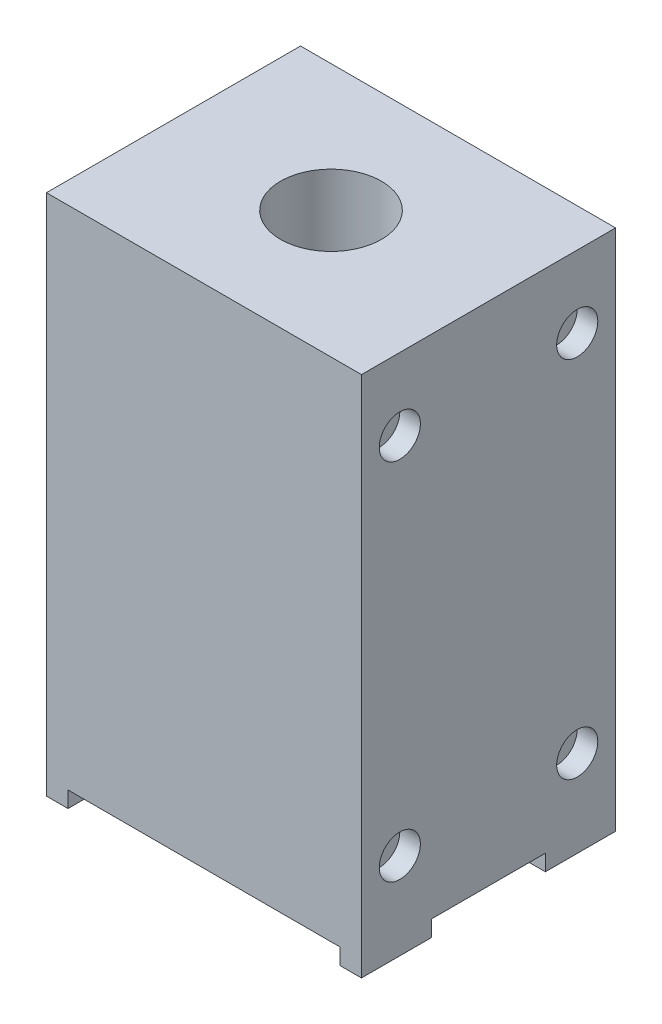
SolidWorks part; units mm, degrees
ref_plane "Front Plane" through (0, 0, 0) normal (0, 0, 1) x (1, 0, 0)
ref_plane "Top Plane" through (0, 0, 0) normal (0, 1, 0) x (1, 0, 0)
ref_plane "Right Plane" through (0, 0, 0) normal (1, 0, 0) x (0, 0, -1)
sketch "Sketch2" plane through (0, 0, 0) normal (0, 1, 0) x (1, 0, 0)
  line L1 (-15.325, 12.36) -> (15.325, 12.36)
  line L2 (-15.325, 12.36) -> (-15.325, -12.36)
  line L3 (-15.325, -12.36) -> (15.325, -12.36)
  line L4 (15.325, 12.36) -> (15.325, -12.36)
  line L5 (-15.325, 12.36) -> (15.325, -12.36) construction
  line L6 (-15.325, -12.36) -> (15.325, 12.36) construction
  point P0 (0, 0)
  dimension "D1" = 24.72
  dimension "D2" = 30.65
extrude "Boss-Extrude1" add sketch "Sketch2" along normal blind 49.27
sketch "Sketch12" plane through (0, 0, 0) normal (0, -1, 0) x (1, 0, 0)
  line L1 (-15.325, 12.36) -> (-13.225, 12.36)
  line L2 (-15.325, 12.36) -> (-15.325, 5.53)
  line L3 (-15.325, 5.53) -> (-13.225, 5.53)
  line L4 (-13.225, 12.36) -> (-13.225, 5.53)
  line L5 (-15.325, -12.36) -> (-13.225, -12.36)
  line L6 (-15.325, -12.36) -> (-15.325, -5.53)
  line L7 (-15.325, -5.53) -> (-13.225, -5.53)
  line L8 (-13.225, -12.36) -> (-13.225, -5.53)
  line L9 (15.325, 12.36) -> (13.225, 12.36)
  line L10 (15.325, 12.36) -> (15.325, 5.53)
  line L11 (15.325, 5.53) -> (13.225, 5.53)
  line L12 (13.225, 12.36) -> (13.225, 5.53)
  line L13 (15.325, -12.36) -> (13.225, -12.36)
  line L14 (15.325, -12.36) -> (15.325, -5.53)
  line L15 (15.325, -5.53) -> (13.225, -5.53)
  line L16 (13.225, -12.36) -> (13.225, -5.53)
  dimension "D1" = 6.83
  dimension "D2" = 6.83
  dimension "D3" = 6.83
  dimension "D4" = 6.83
  dimension "D5" = 2.1
  dimension "D6" = 2.1
  dimension "D7" = 2.1
  dimension "D8" = 2.1
extrude "Boss-Extrude2" add sketch "Sketch12" along normal blind 1.57
sketch "Sketch4" plane through (0, 49.27, 0) normal (0, 1, 0) x (1, 0, 0)
  circle A0 centre (0, 0) radius 4.91
  dimension "D1" = 9.82
extrude "Cut-Extrude3" cut sketch "Sketch4" against normal blind 22
sketch "Sketch5" plane through (0, 27.27, 0) normal (0, 1, 0) x (1, 0, 0)
  circle A0 centre (0, 0) radius 2
  dimension "D1" = 4
extrude "Cut-Extrude4" cut sketch "Sketch5" against normal blind 5
sketch "Sketch7" plane through (0, 22.27, 0) normal (0, 1, 0) x (1, 0, 0)
  circle A0 centre (0, 0) radius 1.5
  dimension "D1" = 3
extrude "Cut-Extrude5" cut sketch "Sketch7" against normal through all
fillet "Fillet4" radius 3 1 edges at (0, 27.27, 2) first distance on face at (0, 27.27, 2)
fillet "Fillet5" radius 3 1 edges at (0, 22.27, 1.5) first distance on face at (0, 22.27, 1.5)
sketch "Sketch13" plane through (15.325, 0, 0) normal (1, 0, 0) x (0, 0, -1)
  line L0 (-12.36, 49.27) -> (12.36, 49.27) construction
  line L1 (-12.36, 49.27) -> (-12.36, -1.57) construction
  line L2 (12.36, 49.27) -> (12.36, -1.57) construction
  line L3 (12.36, -1.57) -> (5.53, -1.57) construction
  line L4 (-5.53, -1.57) -> (-12.36, -1.57) construction
  circle A0 centre (-8.63, 42.27) radius 2
  circle A1 centre (8.63, 42.27) radius 2
  circle A2 centre (-8.63, 6.87) radius 2
  circle A3 centre (8.63, 6.87) radius 2
  point P18 (0, 0)
  dimension "D1" = 4
  dimension "D2" = 4
  dimension "D3" = 4
  dimension "D4" = 4
  dimension "D5" = 7
  dimension "D6" = 7
  dimension "D7" = 3.73
  dimension "D8" = 3.73
  dimension "D9" = 8.44
  dimension "D10" = 8.44
  dimension "D11" = 3.73
  dimension "D12" = 3.73
extrude "Cut-Extrude6" cut sketch "Sketch13" against normal blind 2
sketch "Sketch14" plane through (15.325, 0, 0) normal (1, 0, 0) x (0, 0, -1)
  line L0 (0, 49.27) -> (0, 0) construction
  line L1 (-12.36, 49.27) -> (12.36, 49.27) construction
equation "\"3。21\"=4.09161"
